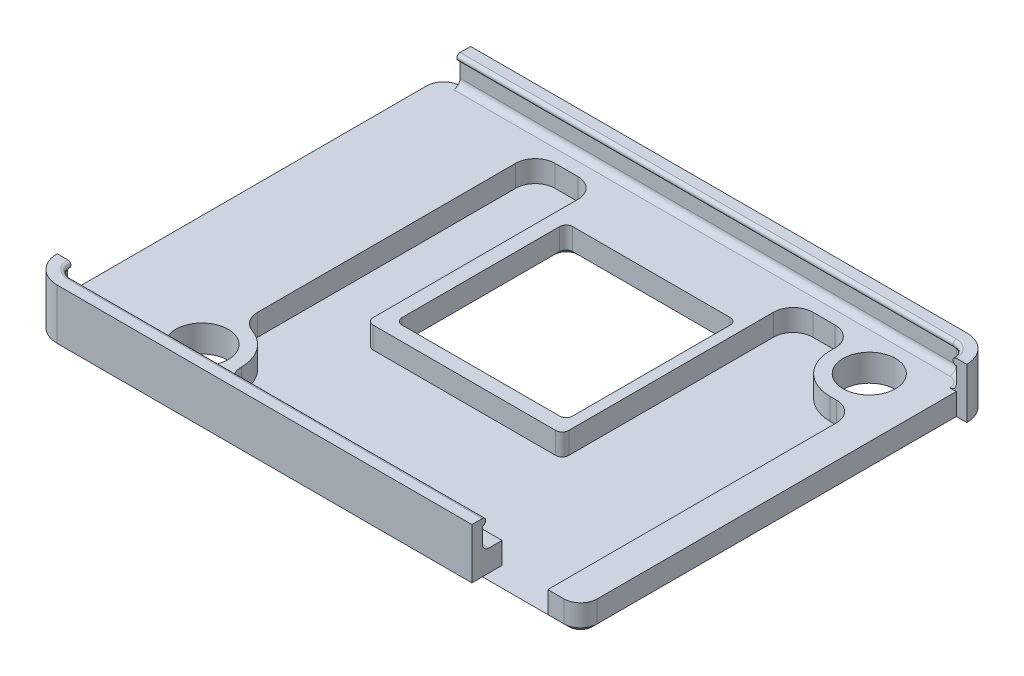
SolidWorks part; units mm, degrees
material "aluminio"
ref_plane "Alzado" through (0, 0, 0) normal (0, 0, 1) x (1, 0, 0)
ref_plane "Planta" through (0, 0, 0) normal (0, 1, 0) x (1, 0, 0)
ref_plane "Vista lateral" through (0, 0, 0) normal (1, 0, 0) x (0, 0, -1)
sketch "Croquis1" plane through (0, 0, 0) normal (0, 1, 0) x (1, 0, 0)
  line L0 (-5.2691, 0.9137) -> (35.0809, 0.9137)
  line L1 (-3.9991, 0.9137) -> (33.4609, 0.9137) construction
  line L2 (-5.2691, 30.8137) -> (35.0809, 30.8137)
  line L3 (26.5809, 3.9137) -> (8.5809, 3.9137) construction
  line L4 (26.5809, 3.9137) -> (26.5809, 27.8137) construction
  line L5 (26.5809, 27.8137) -> (8.5809, 27.8137) construction
  line L6 (8.5809, 3.9137) -> (8.5809, 27.8137) construction
  line L7 (-5.2691, 30.8137) -> (-5.2691, 0.9137)
  line L8 (-5.2691, 4.6637) -> (-5.2691, 26.6637) construction
  line L9 (-5.2691, 0.9137) -> (33.4609, 0.9137) construction
  line L10 (-5.2691, 0.9137) -> (-5.2691, 26.6637) construction
  line L12 (35.0809, 0.9137) -> (35.0809, 30.8137)
  circle A0 centre (3.2309, 3.9137) radius 2
  circle A1 centre (30.5809, 27.4137) radius 2
  dimension "D3" = 4
  dimension "D2" = 29.9
  dimension "D5" = 3
  dimension "D6" = 27.35
  dimension "D7" = 23.5
  dimension "D11" = 8.5
  dimension "D10" = 3
  dimension "D9" = 8.5
  dimension "D8" = 3
  dimension "D12" = 13.85
  dimension "D4" = 40.35
extrude "Saliente-Extruir1" add sketch "Croquis1" along normal blind 2.05
sketch "Croquis2" plane through (0, 2.05, 0) normal (0, 1, 0) x (1, 0, 0)
  line L0 (-5.2691, 0.9137) -> (35.0809, 0.9137) construction
  line L1 (27.5809, 27.4137) -> (27.5809, 29.3137)
  line L3 (3.2309, 2.4137) -> (27.6, 2.4137)
  line L4 (32.5809, 24.4137) -> (32.5809, 0.9137)
  line L5 (35.0809, 0.9137) -> (35.0809, 30.8137) construction
  line L6 (7.9809, 26.6137) -> (22.8809, 26.6137) construction
  line L7 (30.5809, 24.4137) -> (32.5809, 24.4137)
  line L8 (3.2309, 29.3137) -> (3.2309, 2.4137)
  line L9 (7.9809, 26.6137) -> (7.9809, 29.3137)
  line L10 (8.7809, 25.8137) -> (22.0809, 25.8137) construction
  line L11 (8.7809, 25.8137) -> (8.7809, 12.5137) construction
  line L12 (35.0809, 30.8137) -> (-5.2691, 30.8137) construction
  line L13 (27.6, 2.4137) -> (27.6, 0.9137)
  line L14 (27.6, 0.9137) -> (32.5809, 0.9137)
  line L15 (8.7809, 12.5137) -> (22.0809, 12.5137) construction
  line L16 (22.0809, 25.8137) -> (22.0809, 12.5137) construction
  line L17 (22.8809, 26.6137) -> (22.8809, 11.7137)
  line L18 (7.9809, 11.7137) -> (22.8809, 11.7137)
  line L19 (7.9809, 26.6137) -> (7.9809, 11.7137)
  line L20 (7.9809, 26.6137) -> (7.9809, 11.7137) construction
  line L21 (22.8809, 26.6137) -> (22.8809, 11.7137) construction
  line L22 (27.5809, 29.3137) -> (22.8809, 29.3137)
  line L23 (22.8809, 26.6137) -> (22.8809, 29.3137)
  line L24 (7.9809, 29.3137) -> (3.2309, 29.3137)
  circle A0 centre (3.2309, 3.9137) radius 2 construction
  circle A1 centre (3.2309, 3.9137) radius 2 construction
  circle A2 centre (30.5809, 27.4137) radius 2 construction
  circle A3 centre (30.5809, 27.4137) radius 2 construction
  arc A4 (27.5809, 27.4137) -> (30.5809, 24.4137) centre (30.5809, 27.4137) ccw
  circle A6 centre (30.5809, 27.4137) radius 3 construction
  point P8 (33.85, 26.5)
  dimension "D2" = 2.5
  dimension "D6" = 1.5
  dimension "D7" = 13.3
  dimension "D8" = 13.3
  dimension "D9" = 5
  dimension "D10" = 13
  dimension "D5" = 1.5
  dimension "D13" = 1
extrude "Cortar-Extruir2" cut sketch "Croquis2" against normal blind 1.65
sketch "Croquis3" plane through (0, 2.05, 0) normal (0, 1, 0) x (1, 0, 0)
  line L1 (9.0809, 12.8137) -> (22.0809, 12.8137)
  line L2 (9.0809, 12.8137) -> (9.0809, 25.8137)
  line L3 (9.0809, 25.8137) -> (22.0809, 25.8137)
  line L4 (22.0809, 12.8137) -> (22.0809, 25.8137)
  line L8 (35.0809, 0.9137) -> (35.0809, 30.8137) construction
  line L9 (35.0809, 30.8137) -> (-5.2691, 30.8137) construction
  dimension "D1" = 13
  dimension "D2" = 13
  dimension "D3" = 13
  dimension "D4" = 5
extrude "Cortar-Extruir3" cut sketch "Croquis3" against normal through all
fillet "Redondeo2" radius 0.5 4 edges at (22.0809, 1.025, -25.8137) (22.0809, 1.025, -12.8137) (9.0809, 1.025, -12.8137) (9.0809, 1.025, -25.8137)
chamfer "Chaflán1" distance 0.4 angle 45 8 edges at (22.0809, 0, -19.3137) (21.9345, 0, -25.6672) (21.9345, 0, -12.9601) (15.5809, 0, -25.8137) (15.5809, 0, -12.8137) (9.2273, 0, -25.6672) (9.2273, 0, -12.9601) (9.0809, 0, -19.3137)
fillet "Redondeo4" radius 1.27 4 edges at (-5.2691, 1.025, -30.8137) (-5.2691, 1.025, -0.9137) (35.0809, 1.025, -0.9137) (35.0809, 1.025, -30.8137)
sketch "Croquis6" plane through (0, 2.05, 0) normal (0, 1, 0) x (1, 0, 0)
  line L5 (33.8109, 30.8137) -> (-3.9991, 30.8137) construction
  line L7 (-3.9991, 0.9137) -> (27.6, 0.9137) construction
  line L8 (33.8109, 30.8137) -> (-3.9991, 30.8137)
  line L10 (-3.9991, 0.9137) -> (27.6, 0.9137)
  line L11 (33.8109, 31.6137) -> (-3.9991, 31.6137)
  line L12 (-3.9991, 0.1137) -> (27.6, 0.1137)
  line L13 (-3.9991, 30.8137) -> (-3.9991, 31.6137)
  line L14 (-6.0691, 2.1837) -> (-5.2691, 2.1837)
  line L15 (27.6, 0.1137) -> (27.6, 0.9137)
  line L16 (35.8809, 29.5437) -> (35.0809, 29.5437)
  arc A4 (35.0809, 29.5437) -> (33.8109, 30.8137) centre (33.8109, 29.5437) ccw construction
  arc A6 (-5.2691, 2.1837) -> (-3.9991, 0.9137) centre (-3.9991, 2.1837) ccw construction
  arc A7 (35.0809, 29.5437) -> (33.8109, 30.8137) centre (33.8109, 29.5437) ccw
  arc A9 (-5.2691, 2.1837) -> (-3.9991, 0.9137) centre (-3.9991, 2.1837) ccw
  arc A10 (35.8809, 29.5437) -> (33.8109, 31.6137) centre (33.8109, 29.5437) ccw
  arc A12 (-6.0691, 2.1837) -> (-3.9991, 0.1137) centre (-3.9991, 2.1837) ccw
  arc A14 (-3.9991, 31.6137) -> (-6.0691, 29.5437) centre (-3.9991, 29.5437) ccw construction
  arc A15 (-3.9991, 30.8137) -> (-5.2691, 29.5437) centre (-3.9991, 29.5437) ccw construction
  dimension "D1" = 0.8
extrude "Saliente-Extruir3" add sketch "Croquis6" along normal blind 2.2 and the other way up to surface
sketch "Croquis7" plane through (0, 0.4, 0) normal (0, 1, 0) x (1, 0, 0)
  line L0 (0.2309, 3.9137) -> (0.2309, 0.9137)
  line L2 (6.2309, 3.9137) -> (6.2309, 0.9137)
  line L4 (0.2309, 0.9137) -> (6.2309, 0.9137)
  line L5 (-3.9991, 0.9137) -> (27.6, 0.9137) construction
  arc A1 (4.5538, 2.4137) -> (3.2309, 5.9137) centre (3.2309, 3.9137) ccw construction
  arc A3 (6.2309, 3.9137) -> (0.2309, 3.9137) centre (3.2309, 3.9137) ccw
  arc A4 (4.5538, 2.4137) -> (3.2309, 5.9137) centre (3.2309, 3.9137) ccw
  dimension "D1" = 3
extrude "Saliente-Extruir4" add sketch "Croquis7" along normal up to surface (1.65 mm away) up to face at (15.5809, 2.05, -19.3137)
sketch "Croquis9" plane through (0, 0, -29.5437) normal (0, 0, 1) x (1, 0, 0)
  line L0 (35.0809, 2.05) -> (35.0809, 4.25) construction
  circle A0 centre (35.0809, 4) radius 0.25
  dimension "D1" = 0.5
sketch "Croquis10" plane through (0, 4.25, 0) normal (0, 1, 0) x (1, 0, 0)
  line L0 (33.8109, 30.8137) -> (-3.9991, 30.8137) construction
  line L1 (33.8109, 30.8137) -> (-3.9991, 30.8137)
  arc A2 (35.0809, 29.5437) -> (33.8109, 30.8137) centre (33.8109, 29.5437) ccw construction
  arc A3 (35.0809, 29.5437) -> (33.8109, 30.8137) centre (33.8109, 29.5437) ccw
sweep "Barrer1" add profiles "Croquis9" path "Croquis10"
sketch "Croquis11" plane through (0, 0, -2.1837) normal (0, 0, -1) x (-1, 0, 0)
  line L0 (5.2691, 2.05) -> (5.2691, 4.25) construction
  circle A0 centre (5.2691, 4) radius 0.25
  dimension "D1" = 0.5
sketch "Croquis12" plane through (0, 4.25, 0) normal (0, 1, 0) x (1, 0, 0)
  line L0 (-3.9991, 0.9137) -> (27.6, 0.9137) construction
  line L1 (-3.9991, 0.9137) -> (27.6, 0.9137)
  arc A0 (-5.2691, 2.1837) -> (-3.9991, 0.9137) centre (-3.9991, 2.1837) ccw construction
  arc A1 (-5.2691, 2.1837) -> (-3.9991, 0.9137) centre (-3.9991, 2.1837) ccw
sweep "Barrer2" add profiles "Croquis11" path "Croquis12"
fillet "Redondeo6" radius 1.5 7 edges at (3.2309, 1.225, -6.9137) (6.2309, 1.225, -2.4137) (3.2309, 1.225, -29.3137) (7.9809, 1.225, -29.3137) (22.8809, 1.225, -29.3137) (27.5809, 1.225, -29.3137) (32.5809, 1.225, -24.4137)
fillet "Redondeo7" radius 0.5 2 edges at (22.8809, 1.225, -11.7137) (7.9809, 1.225, -11.7137)
fillet "Redondeo8" radius 0.5 4 edges at (-4.8971, 2.05, -1.2856) (34.7089, 2.05, -30.4417) (11.8004, 2.05, -0.9137) (14.9059, 2.05, -30.8137)
sketch "Croquis13" [suppressed] plane through (0, 2.05, 0) normal (0, 1, 0) x (1, 0, 0)
  line L1 (7.9809, 27.8137) -> (-5.1248, 27.8137)
  line L2 (7.9809, 27.8137) -> (7.9809, 33.3132)
  line L3 (7.9809, 33.3132) -> (-5.1248, 33.3132)
  line L4 (-5.1248, 27.8137) -> (-5.1248, 33.3132)
  arc M15 (3.2309, 27.8137) -> (4.7309, 29.3137) centre (4.7309, 27.8137) cw
  line M16 (4.7309, 29.3137) -> (6.4809, 29.3137)
  arc M17 (6.4809, 29.3137) -> (7.9809, 27.8137) centre (6.4809, 27.8137) cw
  line M36 (33.8109, 30.3137) -> (-3.9991, 30.3137)
  line M37 (-3.9991, 30.3137) -> (-3.9991, 30.8137)
  arc M38 (-3.9991, 30.8137) -> (-5.2691, 29.5437) centre (-3.9991, 29.5437) ccw
extrude "Cortar-Extruir5" [suppressed] cut sketch "Croquis13" along normal up to surface (2.2 mm away) contours L4 L2 L3 M38 M37 M36 | L4 L1 L2 M15 M16 M17 M36 M37 M38 | L1 M17 M16 M15
sketch "Croquis14" [suppressed] plane through (0, 2.05, 0) normal (0, 1, 0) x (1, 0, 0)
  line L1 (-3.9991, 31.6137) -> (7.9809, 31.6137)
  line L2 (-3.9991, 31.6137) -> (-3.9991, 30.8137)
  line L3 (-3.9991, 30.8137) -> (7.9809, 30.8137)
  line L4 (7.9809, 31.6137) -> (7.9809, 30.8137)
extrude "Cortar-Extruir6" [suppressed] cut sketch "Croquis14" against normal blind 10
sketch "Croquis15" plane through (0, 2.05, 0) normal (0, 1, 0) x (1, 0, 0)
  line L1 (3.2309, 27.8137) -> (7.9809, 27.8137)
  line L2 (3.2309, 27.8137) -> (3.2309, 31.7816)
  line L3 (3.2309, 31.7816) -> (7.9809, 31.7816)
  line L4 (7.9809, 27.8137) -> (7.9809, 31.7816)
extrude "Cortar-Extruir7" [suppressed] cut sketch "Croquis15" against normal up to surface (1.65 mm away)
chamfer "Chaflán2" distance 0.4 angle 45 13 edges at (-5.2691, 0, -15.8637) (-5.6691, 0, -2.1837) (-5.4628, 0, -0.7199) (11.8004, 0, -0.1137) (27.6, 0, -0.5137) (30.7054, 0, -0.9137) (34.7089, 0, -1.2856) (35.0809, 0, -15.8637) (35.4809, 0, -29.5437) (35.2746, 0, -31.0074) (14.9059, 0, -31.6137) (-3.9991, 0, -31.2137) (-4.8971, 0, -30.4417)
sketch "Croquis16" plane through (0, 0, -31.6137) normal (0, 0, -1) x (-1, 0, 0)
  line L4 (3.9991, 0.4) -> (3.9991, 4.25)
  line L5 (3.9991, 0.4) -> (3.9991, 4.25)
  line L6 (3.9991, 4.25) -> (-33.8109, 4.25)
  line L7 (-33.8109, 4.25) -> (-33.8109, 0.4)
  line L8 (-33.8109, 0.4) -> (3.9991, 0.4)
  line L9 (-33.8109, 0.4) -> (3.9991, 0.4)
  line L10 (3.9991, 4.25) -> (-33.8109, 4.25)
  line L11 (-33.8109, 4.25) -> (-33.8109, 0.4)
  dimension "D1" = 0
extrude "Prueba ref" [suppressed] add sketch "Croquis16" along normal blind 0.8
sketch "Croquis17" plane through (0, 0, -0.1137) normal (0, 0, 1) x (1, 0, 0)
  line L4 (-3.9991, 0.4) -> (27.6, 0.4)
  line L5 (27.6, 0.4) -> (27.6, 4.25)
  line L6 (27.6, 4.25) -> (-3.9991, 4.25)
  line L7 (-3.9991, 4.25) -> (-3.9991, 0.4)
  line L8 (-3.9991, 0.4) -> (27.6, 0.4)
  line L9 (27.6, 0.4) -> (27.6, 4.25)
  line L10 (27.6, 4.25) -> (-3.9991, 4.25)
  line L11 (-3.9991, 4.25) -> (-3.9991, 0.4)
  dimension "D1" = 0
extrude "Prueba ref 2" [suppressed] add sketch "Croquis17" along normal blind 0.8
equation "\"D9@Croquis1\"=3.50mm+5"
equation "\"D12@Croquis1\"=8.85mm+5"
equation "\"D1@Saliente-Extruir3\"=1.60mm+0.6"
equation "\"D10@Croquis2\"=11.00mm+2"
equation "\"D6@Croquis1\"=27.35mm"
